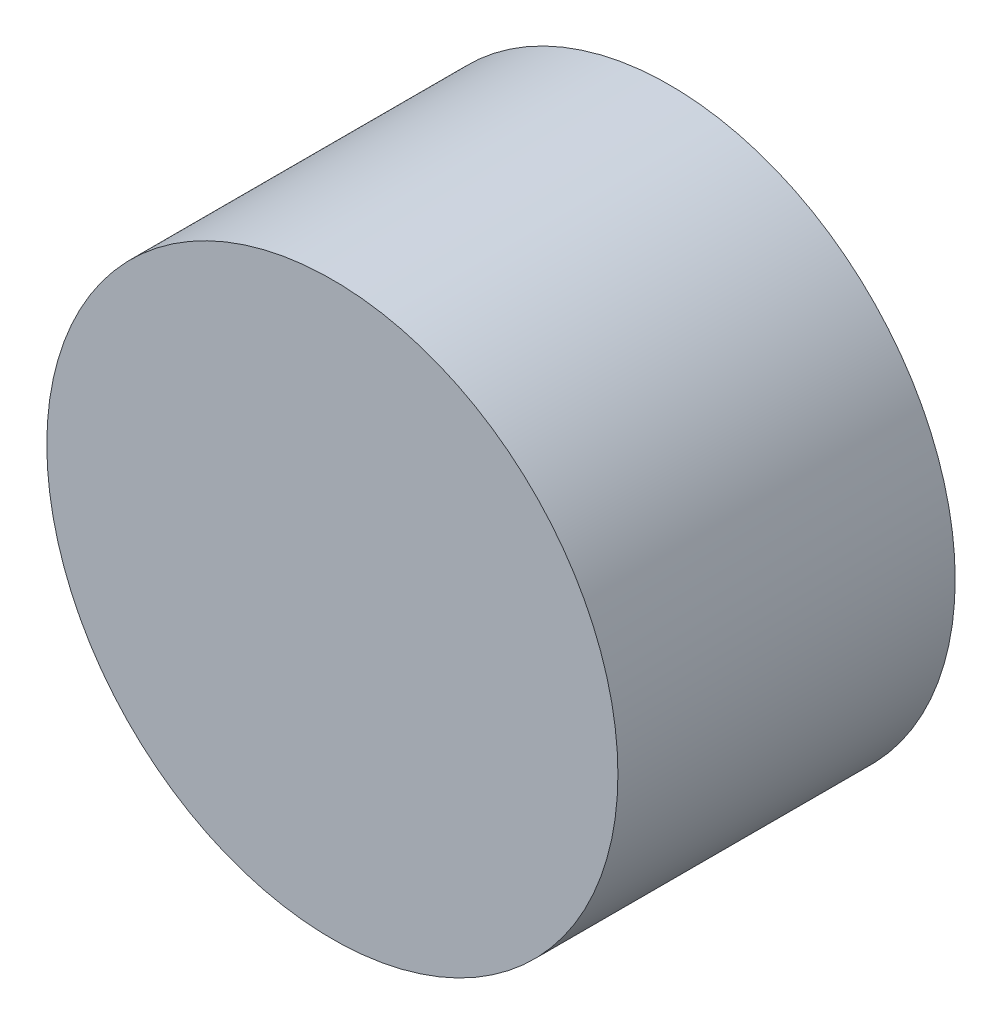
SolidWorks part; units mm, degrees
material "POLYURETHANE (11671)"
ref_plane "Front Plane" through (0, 0, 0) normal (0, 0, 1) x (1, 0, 0)
ref_plane "Top Plane" through (0, 0, 0) normal (0, 1, 0) x (1, 0, 0)
ref_plane "Right Plane" through (0, 0, 0) normal (1, 0, 0) x (0, 0, -1)
sketch "Sketch1" plane through (0, 0, 0) normal (0, 0, 1) x (1, 0, 0)
  circle A0 centre (0, 0) radius 25.4
  dimension "D1" = 50.8
extrude "Boss-Extrude1" add sketch "Sketch1" along normal blind 30
